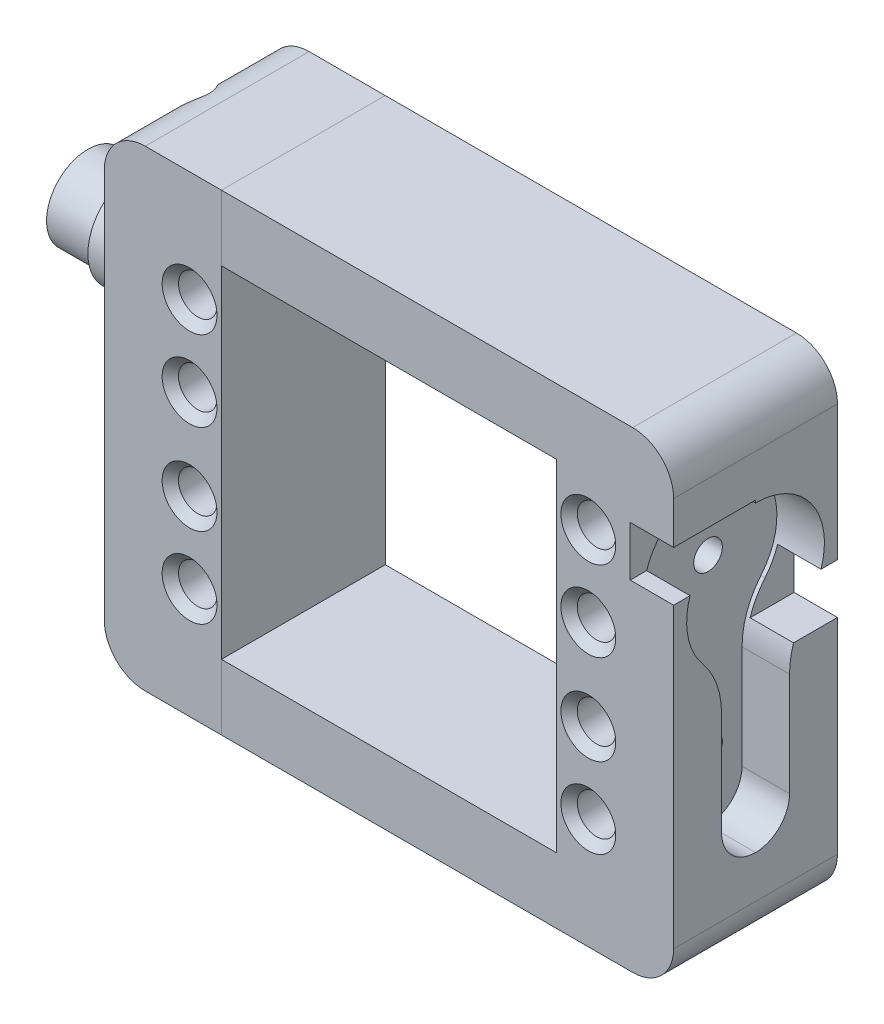
SolidWorks part; units mm, degrees
material "ABS"
ref_plane "Front Plane" through (0, 0, 0) normal (0, 0, 1) x (1, 0, 0)
ref_plane "Top Plane" through (0, 0, 0) normal (0, 1, 0) x (1, 0, 0)
ref_plane "Right Plane" through (0, 0, 0) normal (1, 0, 0) x (0, 0, -1)
sketch "Sketch1" plane through (0, 0, 0) normal (1, 0, 0) x (0, 0, -1)
  line L1 (-10, 10) -> (10, 10)
  line L2 (-10, 10) -> (-10, -10)
  line L3 (-10, -10) -> (10, -10)
  line L4 (10, 10) -> (10, -10)
  line L5 (-10, 10) -> (10, -10) construction
  line L6 (-10, -10) -> (10, 10) construction
  point P0 (0, 0)
  dimension "D1" = 20
  dimension "D2" = 20
extrude "Boss-Extrude1" add sketch "Sketch1" along normal blind 20
sketch "Sketch2" plane through (20, 0, 0) normal (1, 0, 0) x (0, 0, -1)
  line L1 (-10, 35) -> (10, 35)
  line L2 (-10, 35) -> (-10, -35)
  line L3 (-10, -35) -> (10, -35)
  line L4 (10, 35) -> (10, -35)
  line L5 (-10, 35) -> (10, -35) construction
  line L6 (-10, -35) -> (10, 35) construction
  point P0 (0, 0)
  dimension "D1" = 20
  dimension "D2" = 70
extrude "Boss-Extrude2" add sketch "Sketch2" along normal blind 10.3
sketch "Sketch4" plane through (30.3, 0, 0) normal (1, 0, 0) x (0, 0, -1)
  line L0 (0, 7.65) -> (0, 8.1702) construction
  line L1 (7.65, 7.65) -> (-7.65, 7.65) construction
  line L17 (4.15, -26.55) -> (-4.15, -26.55) construction
  line L18 (-7.65, 7.65) -> (7.65, 7.65) construction
  line L22 (-7.65, 7.65) -> (-7.65, -27.55) construction
  line L23 (-7.65, -27.55) -> (7.65, -27.55) construction
  line L24 (7.65, 7.65) -> (7.65, -27.55) construction
  line L25 (-7.65, 7.65) -> (7.65, -27.55) construction
  line L26 (-7.65, -27.55) -> (7.65, 7.65) construction
  line L27 (4.15, -26.55) -> (4.15, -28.55) construction
  line L28 (4.15, -28.55) -> (-4.15, -28.55) construction
  line L29 (-4.15, -26.55) -> (-4.15, -28.55) construction
  line L30 (4.15, -26.55) -> (-4.15, -28.55) construction
  line L31 (4.15, -28.55) -> (-4.15, -26.55) construction
  line L34 (4.15, -28.55) -> (-4.15, -28.55)
  line L35 (-4.15, -28.55) -> (-4.15, -7.3118)
  line L36 (4.15, -28.55) -> (4.15, -7.3118)
  arc A1 (4.15, -6.4265) -> (-4.15, -6.4265) centre (0, 0) ccw construction
  arc A2 (4.15, -7.3118) -> (-4.15, -7.3118) centre (0, 0) ccw
  point P1 (0, -27.55)
  point P7 (0, -13.75)
  point P10 (0, 7.65)
  point P14 (0, -9.95)
  dimension "D1" = 15.3
  dimension "D5" = 2
  dimension "D2" = 15.3
  dimension "D3" = 35.2
  dimension "D4" = 8.3
extrude "Cut-Extrude1" cut sketch "Sketch4" against normal blind 5.8
fillet "Fillet1" radius 4.15 2 edges at (27.4, -28.55, 4.15) (27.4, -28.55, -4.15)
fillet "Fillet2" radius 10 2 edges at (27.4, -7.3118, 4.15) (27.4, -7.3118, -4.15)
sketch "Sketch5" plane through (0, 0, 0) normal (-1, 0, 0) x (0, 0, 1)
  circle A0 centre (0, 0) radius 1.75
  dimension "D1" = 3.5
extrude "Cut-Extrude2" cut sketch "Sketch5" against normal through all
sketch "Sketch6" plane through (24.5, 0, 0) normal (1, 0, 0) x (0, 0, -1)
  line L0 (0, -19.35) -> (0, 0) construction
  line L1 (0, -25.65) -> (0, -23.15) construction
  line L2 (0, -23.15) -> (0, -21.85) construction
  line L3 (0, -21.85) -> (0, -19.35) construction
  line L5 (0, 0) -> (1.164, 0) construction
  line L6 (0, 0) -> (0, -9.35) construction
  line L7 (0, -9.35) -> (1.164, -9.35) construction
  line L8 (1.164, 0) -> (1.164, -9.35) construction
  line L9 (0, 0) -> (1.164, -9.35) construction
  line L10 (0, -9.35) -> (1.164, 0) construction
  circle A0 centre (0, -20.6) radius 1.75
  circle A1 centre (0, -9.35) radius 1.75 construction
  point P11 (0.582, -4.675)
  dimension "D5" = 3.5
  dimension "D6" = 9.35
  dimension "D7" = 3.5
  dimension "D1" = 19.35
  dimension "D2" = 2.5
  dimension "D3" = 1.3
  dimension "D4" = 2.5
extrude "Cut-Extrude3" cut sketch "Sketch6" against normal up to next
sketch "Sketch13" plane through (0, 0, 0) normal (-1, 0, 0) x (0, 0, 1)
  line L1 (-10, 10) -> (10, 10)
  line L2 (-10, 10) -> (-10, -10)
  line L3 (-10, -10) -> (10, -10)
  line L4 (10, 10) -> (10, -10)
extrude "Cut-Extrude9" cut sketch "Sketch13" against normal up to surface (20 mm away) up to face at (20, 22.5, 0)
sketch "Sketch29" plane through (30.3, 0, 0) normal (1, 0, 0) x (0, 0, -1)
  line L0 (0, 0) -> (0, 2.6) construction
  line L1 (15.1094, -8.7) -> (15.1094, -2.6)
  line L2 (0, 2.6) -> (-15.1094, 2.6)
  line L4 (0, 2.6) -> (0, 3.8)
  line L5 (0, 3.8) -> (0, 7.5)
  line L6 (0, 7.5) -> (0, 8.7)
  line L7 (0, 8.7) -> (-15.1094, 8.7)
  line L8 (-15.1094, 8.7) -> (-15.1094, 2.6)
  line L9 (0, -2.6) -> (15.1094, -2.6)
  line L10 (0, -2.6) -> (0, -3.8)
  line L11 (0, -3.8) -> (0, -7.5)
  line L12 (0, -7.5) -> (0, -8.7)
  line L13 (0, -8.7) -> (15.1094, -8.7)
  point P19 (0, 0)
  dimension "D1" = 2.6
  dimension "D2" = 1.2
  dimension "D3" = 3.7
  dimension "D4" = 1.2
  dimension "D5" = 2
extrude "Cut-Extrude18" cut sketch "Sketch29" against normal blind 5.3
sketch "Sketch32" plane through (30.3, 0, 0) normal (1, 0, 0) x (0, 0, -1)
  line L0 (0, -28.55) -> (0, -38.725) construction
  line L1 (10, -35) -> (10, -8.7) construction
  line L2 (-10, -35) -> (10, -35)
  line L3 (-10, -35) -> (-10, -38.725)
  line L4 (-10, -38.725) -> (10, -38.725)
  line L5 (10, -35) -> (10, -38.725)
  dimension "D1" = 10.175
extrude "Boss-Extrude3" add sketch "Sketch32" against normal up to surface (10.3 mm away) up to face at (20, 0, 0)
sketch "Sketch31" plane through (30.3, 0, 0) normal (1, 0, 0) x (0, 0, -1)
  line L2 (0, 8.7) -> (0, 18.875) construction
  line L3 (10, -2.6) -> (10, 35) construction
  line L4 (-10, 35) -> (10, 35)
  line L5 (-10, 35) -> (-10, 18.875)
  line L6 (-10, 18.875) -> (10, 18.875)
  line L7 (10, 35) -> (10, 18.875)
  dimension "D1" = 10.175
extrude "Cut-Extrude19" cut sketch "Sketch31" against normal through all
sketch "Sketch34" plane through (20, 0, 0) normal (-1, 0, 0) x (0, 0, 1)
  line L4 (10, -38.725) -> (10, 18.875)
  line L5 (10, 18.875) -> (-10, 18.875)
  line L6 (-10, 18.875) -> (-10, -38.725)
  line L7 (-10, -38.725) -> (10, -38.725)
  line L8 (10, -38.725) -> (10, 18.875)
  line L9 (10, 18.875) -> (-10, 18.875)
  line L10 (-10, 18.875) -> (-10, -38.725)
  line L11 (-10, -38.725) -> (10, -38.725)
  circle A0 centre (0, -20.6) radius 1.75 construction
  circle A1 centre (0, 0) radius 1.75 construction
  circle A2 centre (0, -20.6) radius 1.75
  circle A3 centre (0, 0) radius 1.75
  dimension "D1" = 0
extrude "Boss-Extrude5" add sketch "Sketch34" along normal blind 4
sketch "Sketch35" plane through (16, 0, 0) normal (-1, 0, 0) x (0, 0, 1)
  line L0 (10, -38.725) -> (10, 18.875) construction
  line L1 (-10, 18.875) -> (10, 18.875)
  line L2 (-10, 18.875) -> (-10, 10.875)
  line L3 (-10, 10.875) -> (10, 10.875)
  line L4 (10, 18.875) -> (10, 10.875)
  line L5 (0, 10.875) -> (0, -30.725) construction
  line L6 (-10, -38.725) -> (10, -38.725)
  line L7 (-10, -38.725) -> (-10, -30.725)
  line L8 (-10, -30.725) -> (10, -30.725)
  line L9 (10, -38.725) -> (10, -30.725)
  dimension "D1" = 41.6
extrude "Boss-Extrude6" add sketch "Sketch35" along normal blind 40.9
sketch "Sketch37" plane through (-24.9, 0, 0) normal (-1, 0, 0) x (0, 0, 1)
  line L1 (-10, 18.875) -> (10, 18.875)
  line L2 (-10, 18.875) -> (-10, -38.725)
  line L3 (-10, -38.725) -> (10, -38.725)
  line L4 (10, 18.875) -> (10, -38.725)
extrude "Boss-Extrude7" add sketch "Sketch37" along normal blind 14.3
sketch "Sketch38" plane through (0, 0, 10) normal (0, 0, 1) x (1, 0, 0)
  line L0 (-24.9, 10.875) -> (-24.9, -9.925) construction
  line L1 (-24.9, -9.925) -> (-24.9, -30.725) construction
  line L2 (-24.9, -30.725) -> (-24.9, 10.875) construction
  line L3 (-24.9, -9.925) -> (-39.2, -9.925) construction
  line L4 (-39.2, -38.725) -> (-39.2, 18.875) construction
  line L5 (-24.9, 0.475) -> (-28.79, 0.475) construction
  line L6 (-28.79, 0.475) -> (-28.79, 5.375) construction
  line L7 (-24.9, 10.875) -> (16, 10.875) construction
  line L8 (-4.45, 10.875) -> (-4.45, -38.725) construction
  line L9 (-39.2, -38.725) -> (30.3, -38.725) construction
  circle A0 centre (-28.79, 5.375) radius 2.35
  circle A1 centre (-28.79, -4.425) radius 2.35
  circle A2 centre (-28.79, -25.225) radius 2.35
  circle A3 centre (-28.79, -15.425) radius 2.35
  circle A4 centre (19.89, 5.375) radius 2.35
  circle A5 centre (19.89, -4.425) radius 2.35
  circle A6 centre (19.89, -15.425) radius 2.35
  circle A7 centre (19.89, -25.225) radius 2.35
  dimension "D4" = 4.7
  dimension "D1" = 41.6
  dimension "D2" = 3.89
  dimension "D3" = 4.9
extrude "Cut-Extrude20" cut sketch "Sketch38" against normal blind 8
chamfer "Chamfer1" distance 1 angle 45 8 edges at (22.24, -25.225, 10) (17.54, -15.425, 10) (22.24, -4.425, 10) (17.54, 5.375, 10) (-26.44, 5.375, 10) (-26.44, -15.425, 10) (-31.14, -25.225, 10) (-31.14, -4.425, 10)
sketch "Sketch41" plane through (16, 0, 0) normal (-1, 0, 0) x (0, 0, 1)
  circle A0 centre (0, 0) radius 3.5
  circle A1 centre (0, -20.6) radius 3.5
  dimension "D1" = 7
  dimension "D2" = 7
extrude "Cut-Extrude23" cut sketch "Sketch41" against normal blind 4
sketch "Sketch42" plane through (-39.2, 0, 0) normal (-1, 0, 0) x (0, 0, 1)
  line L0 (10, -38.725) -> (10, 18.875) construction
  line L1 (-10, -38.725) -> (10, -38.725) construction
  line L2 (-10, -38.725) -> (-10, -30.725) construction
  line L3 (-10, -30.725) -> (10, -30.725) construction
  line L4 (10, -38.725) -> (10, -30.725) construction
  line L5 (-10, -9.925) -> (10, -9.925) construction
  line L6 (-10, 18.875) -> (-10, -38.725) construction
  circle A0 centre (0, -34.725) radius 1.75
  circle A1 centre (0, 14.875) radius 1.75
  point P9 (-10, -34.725)
  dimension "D2" = 3.5
  dimension "D1" = 8
  dimension "D3" = 4
  dimension "D4" = 10
extrude "Cut-Extrude24" cut sketch "Sketch42" against normal blind 22.3
sketch "Sketch43" plane through (-39.2, 0, 0) normal (-1, 0, 0) x (0, 0, 1)
  circle A0 centre (0, 14.875) radius 3.5
  circle A1 centre (0, -34.725) radius 3.5
  dimension "D1" = 7
  dimension "D2" = 7
extrude "Cut-Extrude25" cut sketch "Sketch43" against normal blind 11
fillet "Fillet3" radius 5 4 edges at (-39.2, -38.725, 0) (30.3, -38.725, 0) (30.3, 18.875, 0) (-39.2, 18.875, 0)
sketch "Sketch44" plane through (0, 0, 10) normal (0, 0, 1) x (1, 0, 0)
  line L0 (-24.9, 18.875) -> (-24.9, -38.725)
  line L1 (-34.2, 18.875) -> (25.3, 18.875) construction
  line L2 (-34.2, -38.725) -> (25.3, -38.725) construction
split "Split1" trim tools "Sketch44" bodies to split 171 resulting bodies 172 173
sketch "Sketch45" plane through (-24.9, 0, 0) normal (-1, 0, 0) x (0, 0, 1)
  circle A0 centre (0, 14.875) radius 2.35
  circle A1 centre (0, -34.725) radius 2.35
  dimension "D1" = 4.7
  dimension "D2" = 4.7
extrude "Cut-Extrude26" cut sketch "Sketch45" against normal blind 8
chamfer "Chamfer2" distance 1 angle 45 2 edges at (-24.9, -34.725, 2.35) (-24.9, 14.875, 2.35)
sketch "Sketch46" plane through (-39.2, 0, 0) normal (-1, 0, 0) x (0, 0, 1)
  circle A1 centre (0, 0) radius 5.05
  dimension "D1" = 10.1
extrude "Boss-Extrude8" add sketch "Sketch46" along normal blind 12
sketch "Sketch50" plane through (-39.2, 0, 0) normal (-1, 0, 0) x (0, 0, 1)
  circle A0 centre (0, 0) radius 6
  dimension "D1" = 12
extrude "Boss-Extrude9" add sketch "Sketch50" along normal blind 6
fillet "Fillet6" radius 3 1 edges at (-39.2, 0, 6)
mirror "Mirror1" [suppressed] of bodies 177 174 167 172 173
delete or keep bodies "Body-Delete/Keep 1" [suppressed] type delete bodies bodies 177 174
sketch "Sketch47" plane through (0, 0, 10) normal (0, 0, 1) x (1, 0, 0)
  line L0 (19.89, 5.375) -> (19.89, -4.425)
  line L1 (19.89, 0.475) -> (28.8988, 0.475)
sketch "Sketch48" plane through (24.5, 0, 0) normal (1, 0, 0) x (0, 0, -1)
  line L0 (0, 0) -> (-13.129, 0)
sketch "Sketch49" plane through (0, 0, 10) normal (0, 0, 1) x (1, 0, 0)
  line L0 (24.5491, 0) -> (24.5491, 0.475)
  line L1 (19.89, 0.475) -> (28.8988, 0.475) construction
